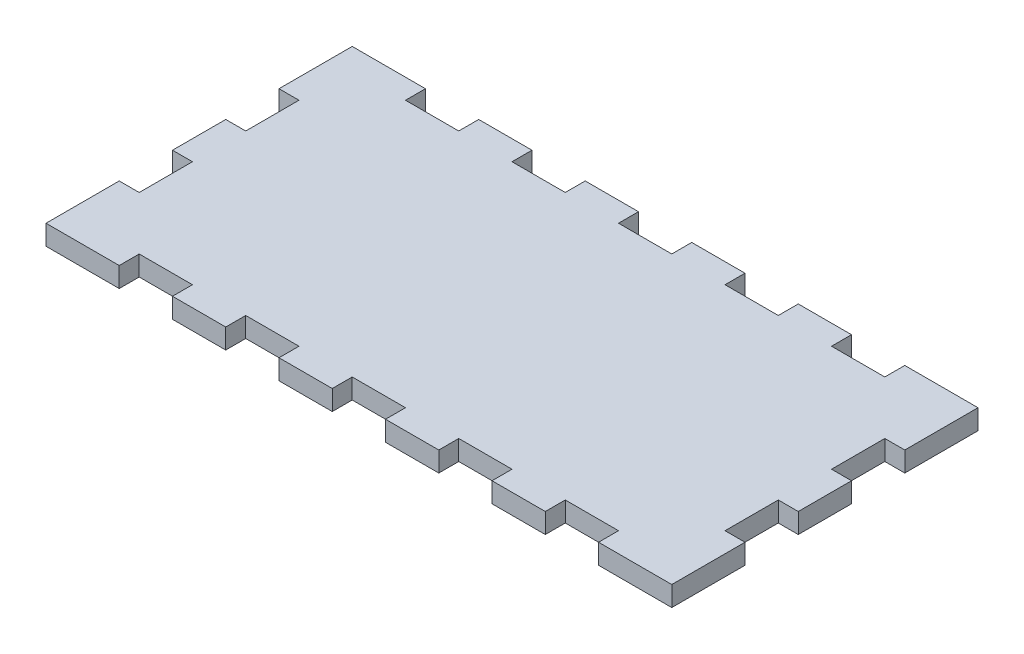
SolidWorks part; units mm, degrees
ref_plane "Front Plane" through (0, 0, 0) normal (0, 0, 1) x (1, 0, 0)
ref_plane "Top Plane" through (0, 0, 0) normal (0, 1, 0) x (1, 0, 0)
ref_plane "Right Plane" through (0, 0, 0) normal (1, 0, 0) x (0, 0, -1)
sketch "Sketch2" plane through (0, 0, 0) normal (0, 1, 0) x (1, 0, 0)
  line L1 (139.7, -63.5) -> (-139.7, -63.5)
  line L2 (139.7, -63.5) -> (139.7, 63.5)
  line L3 (139.7, 63.5) -> (-139.7, 63.5)
  line L4 (-139.7, -63.5) -> (-139.7, 63.5)
  line L5 (139.7, -63.5) -> (-139.7, 63.5) construction
  line L6 (139.7, 63.5) -> (-139.7, -63.5) construction
  point P0 (0, 0)
  dimension "D1" = 279.4
  dimension "D2" = 127
extrude "Boss-Extrude1" add sketch "Sketch2" along normal blind 9.525
sketch "Sketch3" plane through (0, 0, 63.5) normal (0, 0, 1) x (1, 0, 0)
  line L0 (-139.7, 9.525) -> (139.7, 9.525) construction
  line L1 (-139.7, 0) -> (-114.3, 0)
  line L2 (-139.7, 0) -> (-139.7, 9.525)
  line L3 (-139.7, 9.525) -> (-114.3, 9.525)
  line L4 (-114.3, 0) -> (-114.3, 9.525)
  dimension "D1" = 25.4
extrude "Boss-Extrude2" add sketch "Sketch3" along normal blind 9.525
pattern_linear "LPattern1" count 6 spacing 50.8 along (1, 0, 0) of "Boss-Extrude2"
mirror "Mirror1" about plane through (0, 0, 0) normal (0, 0, 1) of "LPattern1"
sketch "Sketch4" plane through (139.7, 0, 0) normal (1, 0, 0) x (0, 0, -1)
  line L0 (-73.025, 0) -> (73.025, 0) construction
  line L1 (-63.5, 0) -> (-38.1, 0)
  line L2 (-63.5, 0) -> (-63.5, 9.525)
  line L3 (-63.5, 9.525) -> (-38.1, 9.525)
  line L4 (-38.1, 0) -> (-38.1, 9.525)
  line L5 (-73.025, 9.525) -> (73.025, 9.525) construction
  line L6 (-73.025, 0) -> (-73.025, 9.525) construction
  dimension "D1" = 9.525
  dimension "D2" = 25.4
extrude "Boss-Extrude3" add sketch "Sketch4" along normal blind 9.525
pattern_linear "LPattern2" count 3 spacing 50.8 along (0, 0, -1) of "Boss-Extrude3"
mirror "Mirror2" about plane through (0, 0, 0) normal (1, 0, 0) of "LPattern2"
sketch "Sketch6" plane through (0, 0, 63.5) normal (0, 0, 1) x (1, 0, 0)
  line L1 (149.225, 9.525) -> (139.7, 9.525)
  line L2 (149.225, 9.525) -> (149.225, 0)
  line L3 (149.225, 0) -> (139.7, 0)
  line L4 (139.7, 9.525) -> (139.7, 0)
extrude "Boss-Extrude4" add sketch "Sketch6" along normal blind 9.525
mirror "Mirror3" about plane through (0, 0, 0) normal (1, 0, 0) of "Boss-Extrude4"
mirror "Mirror4" about plane through (0, 0, 0) normal (0, 0, 1) of "Mirror3"
sketch "Sketch7" plane through (0, 9.525, 0) normal (0, 1, 0) x (1, 0, 0)
  circle A0 centre (-29.2864, 23.8119) radius 0.032
  circle A1 centre (-23.072, 14.7922) radius 0.1056
  circle A2 centre (27.5, 22.9863) radius 2
  circle A3 centre (22.5, 12.9863) radius 2
extrude "Cut-Extrude1" [suppressed] cut sketch "Sketch7" against normal through all
sketch "Sketch8" plane through (0, 9.525, 0) normal (0, 1, 0) x (1, 0, 0)
  circle A0 centre (-25.974, 23.4033) radius 0.0509
  circle A1 centre (-24.0521, 14.3728) radius 0.0812
  circle A2 centre (-27.5, 22.9863) radius 2
  circle A3 centre (-22.5, 12.9863) radius 2
extrude "Cut-Extrude3" [suppressed] cut sketch "Sketch8" against normal through all contours A2 A0 | A3
sketch "Sketch9" [suppressed] plane through (0, 0, 0) normal (0, -1, 0) x (1, 0, 0)
  circle A0 centre (-22.5, -12.9863) radius 3.81
  circle A1 centre (-27.5, -22.9863) radius 3.81
  circle A2 centre (22.5, -12.9863) radius 3.81
  circle A3 centre (27.5, -22.9863) radius 3.81
  dimension "D1" = 7.62
  dimension "D2" = 7.62
  dimension "D3" = 7.62
  dimension "D4" = 7.62
extrude "Cut-Extrude4" [suppressed] cut sketch "Sketch9" against normal blind 4.7625
